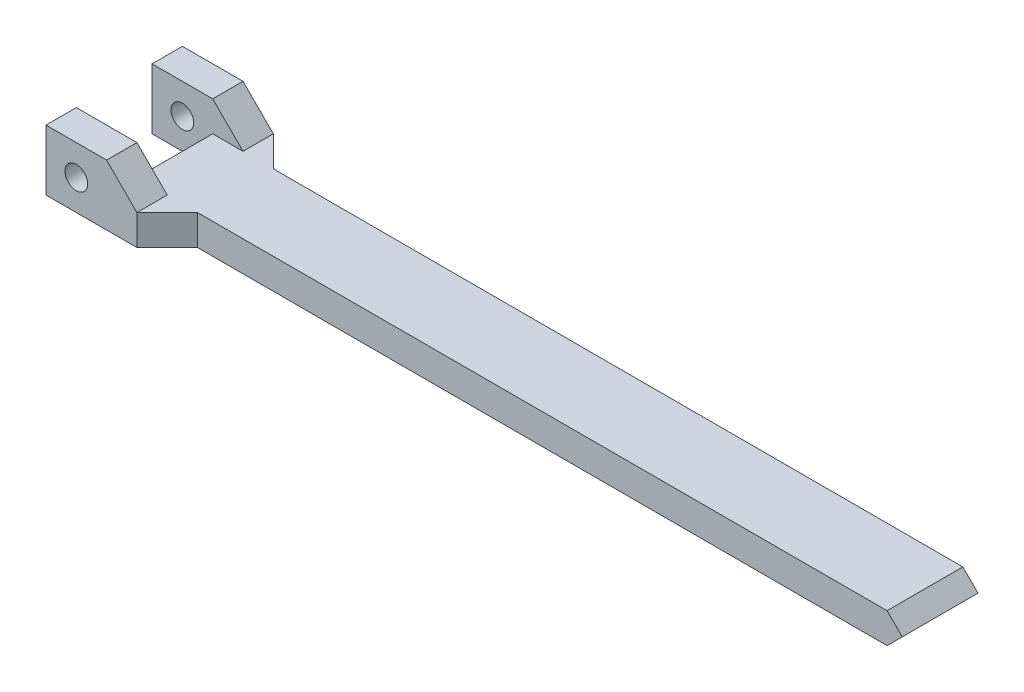
SolidWorks part; units mm, degrees
ref_plane "Płaszczyzna przednia" through (0, 0, 0) normal (0, 0, 1) x (1, 0, 0)
ref_plane "Płaszczyzna górna" through (0, 0, 0) normal (0, 1, 0) x (1, 0, 0)
ref_plane "Płaszczyzna prawa" through (0, 0, 0) normal (1, 0, 0) x (0, 0, -1)
sketch "Szkic1" plane through (0, 0, 0) normal (0, 1, 0) x (1, 0, 0)
  line L1 (-50.5, -5) -> (50.5, -5)
  line L2 (-50.5, -5) -> (-50.5, 5)
  line L3 (-50.5, 5) -> (50.5, 5)
  line L4 (50.5, -5) -> (50.5, 5)
  line L5 (-50.5, -5) -> (50.5, 5) construction
  line L6 (-50.5, 5) -> (50.5, -5) construction
  point P0 (0, 0)
  dimension "D1" = 10
  dimension "D2" = 101
extrude "Dodanie-wyciągnięcie1" add sketch "Szkic1" along normal blind 4
sketch "Szkic2" plane through (-50.5, 0, 0) normal (-1, 0, 0) x (0, 0, 1)
  line L0 (-5, 0) -> (-5, 8)
  line L1 (-9, 0) -> (-5, 0)
  line L2 (-9, 0) -> (-9, 8)
  line L3 (-9, 8) -> (-5, 8)
  line L4 (9, 0) -> (9, 8)
  line L5 (5, 0) -> (5, 8)
  line L6 (-5, 0) -> (5, 0) construction
  line L7 (5, 0) -> (9, 0)
  line L8 (-5, 8) -> (5, 8) construction
  line L9 (5, 8) -> (9, 8)
  dimension "D1" = 18
  dimension "D2" = 8
extrude "Dodanie-wyciągnięcie2" add sketch "Szkic2" along normal blind 8 and the other way blind 4
chamfer "Sfazowanie1" distance 4 angle 45 2 edges at (-46.5, 8, -7) (-46.5, 8, 7)
chamfer "Sfazowanie2" distance 4 angle 45 2 edges at (-46.5, 2, -5) (-46.5, 2, 5)
sketch "Szkic4" plane through (0, 0, 9) normal (0, 0, 1) x (1, 0, 0)
  line L0 (-58.5, 4) -> (-54.5, 4) construction
  line L1 (-58.5, 0) -> (-58.5, 8) construction
  line L2 (-54.5, 4) -> (-54.5, 8) construction
  line L3 (-50.5, 8) -> (-58.5, 8) construction
  circle A0 centre (-54.5, 4) radius 1.5
  point P0 (0, 0)
  point P2 (-54.8414, 4)
  dimension "D1" = 3
extrude "Wytnij-wyciągnięcie1" cut sketch "Szkic4" against normal through all both and the other way through all
chamfer "Sfazowanie3" distance 2 angle 45 2 edges at (50.5, 4, 0) (50.5, 0, 0)
